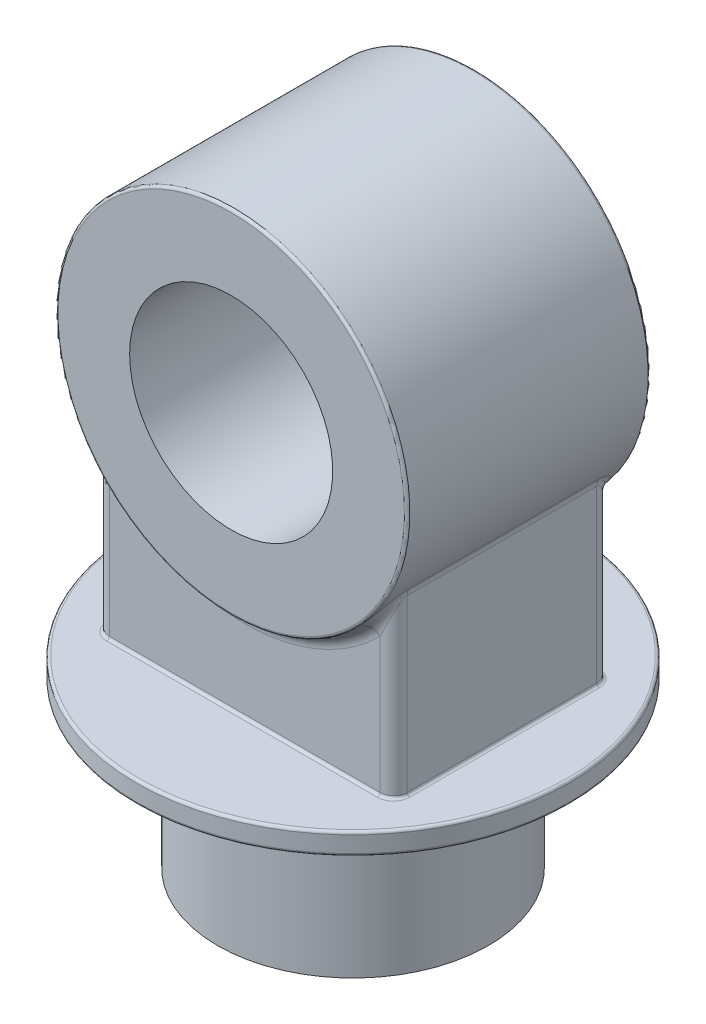
SolidWorks part; units mm, degrees
material "Alloy Steel (SS)"
ref_plane "Front" through (0, 0, 0) normal (0, 0, 1) x (1, 0, 0)
ref_plane "Top" through (0, 0, 0) normal (0, 1, 0) x (1, 0, 0)
ref_plane "Right" through (0, 0, 0) normal (1, 0, 0) x (0, 0, -1)
sketch "Sketch1" plane through (0, 0, 0) normal (0, 1, 0) x (1, 0, 0)
  circle A0 centre (0, 0) radius 100
  dimension "D1" = 200
extrude "Boss-Extrude1" add sketch "Sketch1" along normal blind 120
sketch "Sketch2" plane through (0, 120, 0) normal (0, 1, 0) x (1, 0, 0)
  circle A0 centre (0, 0) radius 160
  dimension "D1" = 320
extrude "Boss-Extrude2" add sketch "Sketch2" along normal blind 16
sketch "Sketch3" plane through (0, 0, 0) normal (0, 0, 1) x (1, 0, 0)
  line L0 (160, 136) -> (-160, 136) construction
  circle A0 centre (0, 336) radius 75
  circle A1 centre (0, 336) radius 130
  dimension "D1" = 260
  dimension "D2" = 150
  dimension "D4" = 200
extrude "Boss-Extrude3" add sketch "Sketch3" along normal mid plane 180 separate body
sketch "Sketch4" plane through (0, 136, 0) normal (0, 1, 0) x (1, 0, 0)
  line L1 (-110, 80) -> (110, 80)
  line L2 (-110, 80) -> (-110, -80)
  line L3 (-110, -80) -> (110, -80)
  line L4 (110, 80) -> (110, -80)
  line L5 (-110, 80) -> (110, -80) construction
  line L6 (-110, -80) -> (110, 80) construction
  point P0 (0, 0)
  dimension "D1" = 160
  dimension "D2" = 220
extrude "Boss-Extrude4" add sketch "Sketch4" along normal up to next
fillet "Fillet1" radius 10 4 edges at (-110, 201.359, -80) (-110, 201.359, 80) (110, 201.359, -80) (110, 201.359, 80)
fillet "Fillet2" radius 10 8 edges at (-107.795, 263.3347, -76.2641) (0, 206, -80) (109.1883, 265.4457, -73.9464) (110, 266.718, 0) (107.795, 263.3347, 76.2641) (0, 206, 80) (-109.1883, 265.4457, 73.9464) (-110, 266.718, 0)
fillet "Fillet3" radius 2 4 edges at (0, 206, -90) (0, 206, 90) (0, 466, -90) (0, 466, 90)
fillet "Fillet4" radius 2 10 edges at (-107.0711, 136, 77.0711) (0, 136, 80) (107.0711, 136, 77.0711) (110, 136, 0) (107.0711, 136, -77.0711) (0, 136, -80) (-107.0711, 136, -77.0711) (-110, 136, 0) (0, 136, 160) (0, 120, 160)
